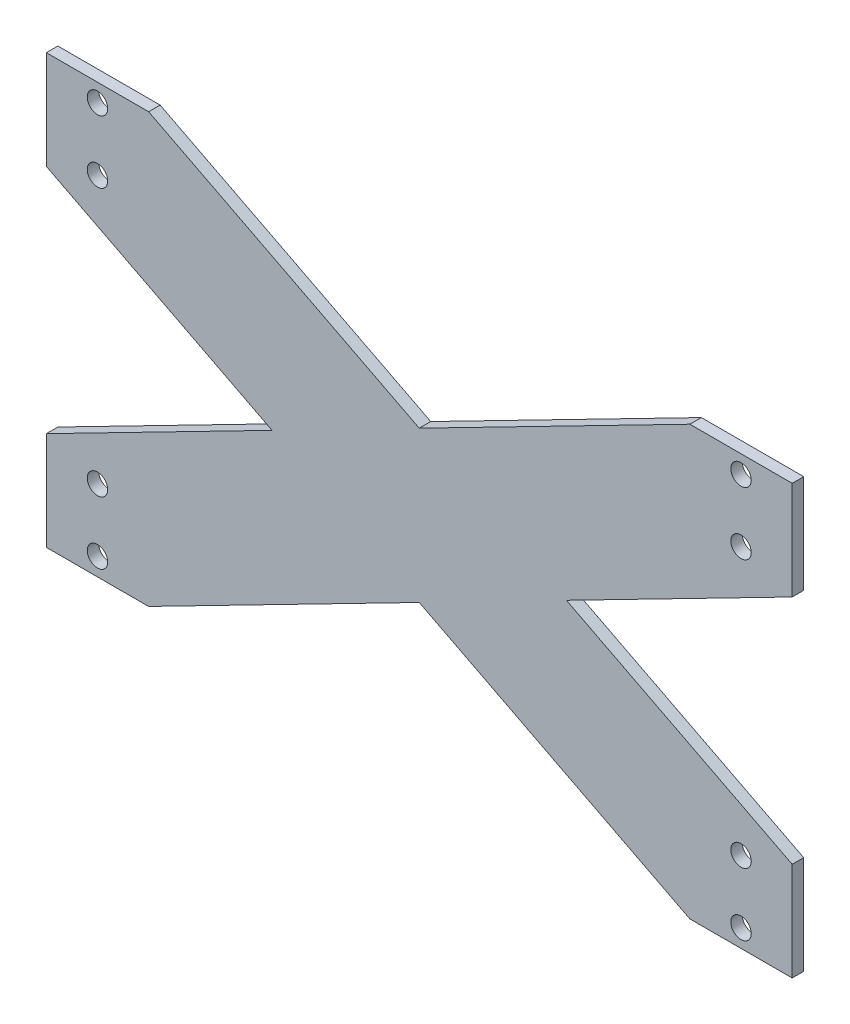
SolidWorks part; units mm, degrees
ref_plane "Front Plane" through (0, 0, 0) normal (0, 0, 1) x (1, 0, 0)
ref_plane "Top Plane" through (0, 0, 0) normal (0, 1, 0) x (1, 0, 0)
ref_plane "Right Plane" through (0, 0, 0) normal (1, 0, 0) x (0, 0, -1)
sketch "Sketch1" plane through (0, 0, 0) normal (0, 0, 1) x (1, 0, 0)
  line L0 (6.342, -18) -> (257.942, -147)
  line L1 (6.342, 20.5) -> (297.942, 20.5)
  line L2 (6.342, 20.5) -> (6.342, -147)
  line L3 (6.342, -147) -> (297.942, -147)
  line L4 (297.942, 20.5) -> (297.942, -147)
  line L5 (297.942, -108.5) -> (46.342, 20.5)
  line L6 (257.942, 20.5) -> (6.342, -108.5)
  line L7 (297.942, -18) -> (46.342, -147)
  circle A0 centre (26.342, 13.5) radius 4
  circle A1 centre (26.342, 13.5) radius 4 construction
  circle A2 centre (26.342, -11) radius 4
  circle A3 centre (26.342, -11) radius 4 construction
  circle A4 centre (26.342, -115.5) radius 4
  circle A5 centre (26.342, -140) radius 4
  circle A6 centre (26.342, -140) radius 4 construction
  circle A7 centre (26.342, -115.5) radius 4 construction
  circle A8 centre (277.942, 13.5) radius 4
  circle A9 centre (277.942, 13.5) radius 4 construction
  circle A10 centre (277.942, -11) radius 4
  circle A11 centre (277.942, -11) radius 4 construction
  circle A12 centre (277.942, -115.5) radius 4
  circle A13 centre (277.942, -115.5) radius 4 construction
  circle A14 centre (277.942, -140) radius 4
  circle A15 centre (277.942, -140) radius 4 construction
extrude "Boss-Extrude1" add sketch "Sketch1" along normal blind 4.5 contours L7 L0 L6 L2 L3 A5 A4 | L7 L5 L6 L0 | L6 L5 L1 L2 L0 A2 A0 | L7 L4 L1 L6 L5 A10 A8 | L5 L7 L0 L3 L4 A14 A12 region at (69.6323, -19.7886, 0) region at (152.142, -63.25, 0) region at (69.6323, -106.7114, 0) region at (234.6517, -106.7114, 0) region at (234.6517, -19.7886, 0)
